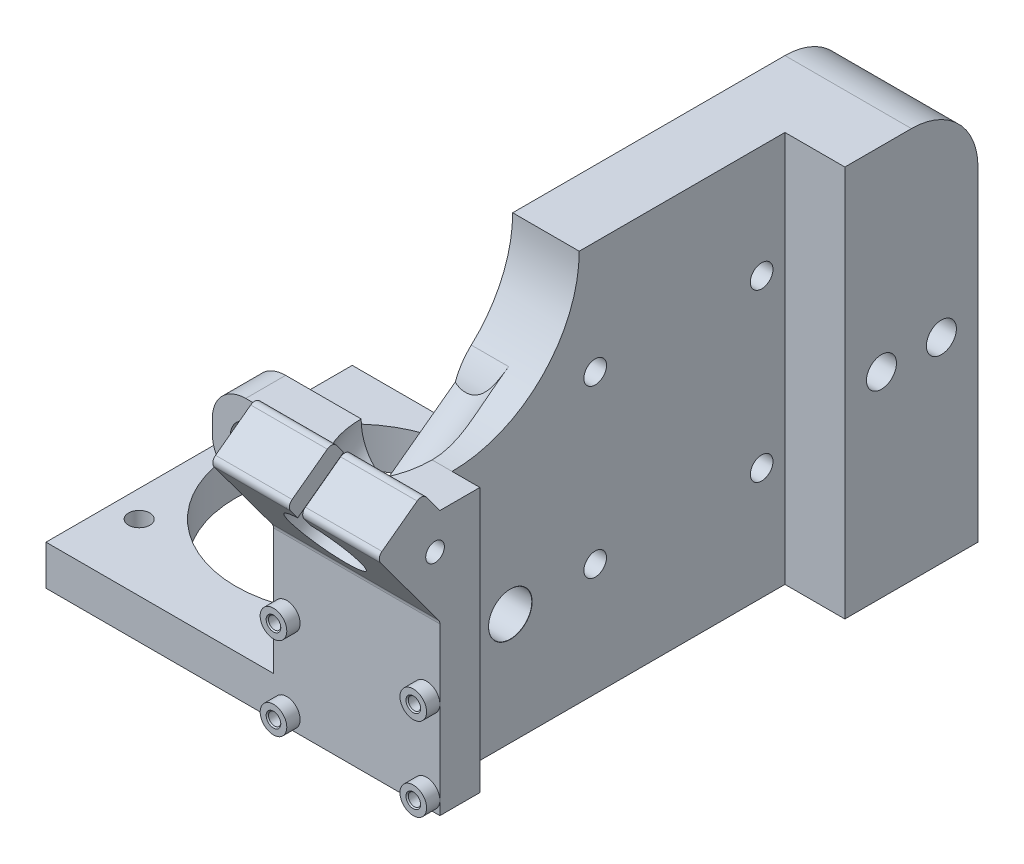
SolidWorks part; units mm, degrees
ref_plane "Front Plane" through (0, 0, 0) normal (0, 0, 1) x (1, 0, 0)
ref_plane "Top Plane" through (0, 0, 0) normal (0, 1, 0) x (1, 0, 0)
ref_plane "Right Plane" through (0, 0, 0) normal (1, 0, 0) x (0, 0, -1)
sketch "Sketch2" plane through (0, 0, 0) normal (0, 0, 1) x (1, 0, 0)
  line L0 (-18.5, 0) -> (18.5, 0) construction
  line L1 (-18.5, 6.1) -> (18.5, 6.1)
  line L2 (-18.5, 6.1) -> (-18.5, -6.1)
  line L3 (-18.5, -6.1) -> (18.5, -6.1)
  line L4 (18.5, 6.1) -> (18.5, -6.1)
  line L5 (-18.5, 6.1) -> (18.5, -6.1) construction
  line L6 (-18.5, -6.1) -> (18.5, 6.1) construction
  circle A0 centre (-5.08, 0) radius 1.5 construction
  circle A1 centre (12.42, 0) radius 1.5
  point P0 (0, 0)
  dimension "D5" = 3
  dimension "D1" = 12.2
  dimension "D2" = 37
  dimension "D3" = 13.42
  dimension "D4" = 17.5
extrude "Boss-Extrude2" add sketch "Sketch2" along normal blind 6
hole_wizard "CBORE for M3 SHCS1" positions "Sketch6" profile "Sketch7" counterbore size "M3" standard "ANSI Metric" end condition through all
sketch "Sketch6" plane through (0, 0, 6) normal (0, 0, 1) x (1, 0, 0)
  point P3 (12.42, 0)
sketch "Sketch7" plane through (12.42, 0, 6) normal (1, 0, 0) x (0, -1, 0)
  line L0 (0, 0) -> (0, 6)
  line L1 (0, 6) -> (1.7, 6)
  line L3 (1.7, 6) -> (1.7, 3)
  line L4 (1.7, 3) -> (3.25, 3)
  line L5 (3.25, 3) -> (3.25, 0)
  line L7 (3.25, 0) -> (0, 0)
  line L11 (0, -6.35) -> (0, 107.95) construction
  dimension "Thru Hole Dia." = 3.4
  dimension "Thru Hole Depth" = 6
  dimension "C'Bore Dia." = 6.5
  dimension "C'Bore Depth" = 3
sketch "Sketch21" plane through (0, 0, 6) normal (0, 0, 1) x (1, 0, 0)
  line L0 (-18.5, -6.1) -> (18.5, -6.1) construction
  line L1 (-12.5, -6.1) -> (-18.5, -6.1)
  line L2 (-12.5, -6.1) -> (-12.5, -27.6)
  line L3 (-12.5, -27.6) -> (-18.5, -27.6)
  line L4 (-18.5, -6.1) -> (-18.5, -27.6)
  point P4 (-18.5, -6.1)
  dimension "D1" = 21.5
  dimension "D2" = 6
extrude "Boss-Extrude6" add sketch "Sketch21" against normal blind 6
sketch "Sketch22" plane through (0, 0, 6) normal (0, 0, 1) x (1, 0, 0)
  line L1 (-18.5, -27.6) -> (21.5, -27.6)
  line L2 (-18.5, -27.6) -> (-18.5, -33.6)
  line L3 (-18.5, -33.6) -> (21.5, -33.6)
  line L4 (21.5, -27.6) -> (21.5, -33.6)
  line L5 (18.5, -6.1) -> (18.5, 6.1) construction
  dimension "D1" = 6
  dimension "D2" = 3
extrude "Boss-Extrude7" add sketch "Sketch22" against normal blind 6
sketch "Sketch23" plane through (0, 0, 6) normal (0, 0, 1) x (1, 0, 0)
  line L0 (-18.5, -33.6) -> (21.5, -33.6) construction
  line L1 (15.67, 6.1) -> (40.67, 6.1)
  line L2 (15.67, 6.1) -> (15.67, -33.6)
  line L3 (15.67, -33.6) -> (40.67, -33.6)
  line L4 (40.67, 6.1) -> (40.67, -33.6)
  line L6 (-18.5, 6.1) -> (-18.5, -33.6) construction
  circle A0 centre (12.42, 0) radius 3.25 construction
  dimension "D1" = 25
extrude "Boss-Extrude8" add sketch "Sketch23" against normal blind 6
sketch "Sketch24" plane through (0, -27.6, 0) normal (0, -1, 0) x (1, 0, 0)
  line L1 (-18.5, 0) -> (21.5, 0)
  line L2 (-18.5, 0) -> (-18.5, -40)
  line L3 (-18.5, -40) -> (21.5, -40)
  line L4 (21.5, 0) -> (21.5, -40)
  line L5 (-18.5, -31.0949) -> (-18.5, -3) construction
  line L6 (21.5, -3) -> (21.5, -19.75) construction
  line L9 (-18.5, 0) -> (40.67, 0) construction
  line L12 (20.3129, -40) -> (-17.3129, -40) construction
  circle A0 centre (17.5, -4) radius 1.25 construction
  circle A1 centre (-14.5, -4) radius 1.55 construction
  circle A2 centre (17.5, -4) radius 1.25 construction
  circle A3 centre (-14.5, -4) radius 1.55 construction
  circle A4 centre (17.5, -36) radius 1.25 construction
  circle A5 centre (17.5, -36) radius 1.25 construction
  circle A6 centre (17.5, -4) radius 1.6
  circle A7 centre (-14.5, -4) radius 1.6
  circle A8 centre (17.5, -36) radius 1.6
  dimension "D1" = 3.2
extrude "Boss-Extrude9" add sketch "Sketch24" along normal up to surface (6 mm away) up to face at (11.085, -33.6, 3)
sketch "Sketch25" plane through (0, -33.6, 0) normal (0, -1, 0) x (1, 0, 0)
  line L0 (21.5, -20) -> (-18.5, -20) construction
  line L1 (21.5, -40) -> (21.5, 0) construction
  line L2 (-18.5, -40) -> (-18.5, 6) construction
  circle A0 centre (1.5, -20) radius 17.5
  dimension "D1" = 35
extrude "Cut-Extrude9" cut sketch "Sketch25" against normal up to next
sketch "Sketch26" plane through (0, 0, 6) normal (0, 0, 1) x (1, 0, 0)
  line L1 (40.67, -33.6) -> (15.67, -33.6) construction
  line L2 (40.67, -33.6) -> (40.67, -9.6) construction
  line L3 (40.67, -9.6) -> (15.67, -9.6) construction
  line L4 (15.67, -33.6) -> (15.67, -9.6) construction
  line L5 (17.67, -31.6) -> (38.67, -31.6) construction
  line L6 (17.67, -31.6) -> (17.67, -19.1) construction
  line L7 (17.67, -19.1) -> (38.67, -19.1) construction
  line L8 (38.67, -31.6) -> (38.67, -19.1) construction
  circle A0 centre (38.67, -31.6) radius 2
  circle A1 centre (17.67, -31.6) radius 2
  circle A2 centre (17.67, -19.1) radius 2
  circle A3 centre (38.67, -19.1) radius 2
  dimension "D1" = 25
  dimension "D2" = 24
  dimension "D3" = 2
  dimension "D4" = 21
  dimension "D5" = 12.5
  dimension "D6" = 2
extrude "Boss-Extrude10" add sketch "Sketch26" along normal blind 2
hole_wizard "M2x0.4 Tapped Hole1" positions "Sketch27" profile "Sketch29" tap size "M2x0.4" standard "ANSI Metric"
sketch "Sketch27" plane through (0, 0, 8) normal (0, 0, 1) x (1, 0, 0)
  circle A0 centre (38.67, -31.6) radius 2 construction
  circle A1 centre (38.67, -19.1) radius 2 construction
  circle A2 centre (17.67, -19.1) radius 2 construction
  circle A3 centre (17.67, -31.6) radius 2 construction
  point P0 (17.67, -31.6)
  point P2 (17.67, -19.1)
  point P4 (38.67, -19.1)
  point P6 (38.67, -31.6)
sketch "Sketch29" plane through (17.67, -31.6, 8) normal (1, 0, 0) x (0, -1, 0)
  line L0 (0, 0) -> (0, 8.5558)
  line L1 (0, 8.5558) -> (0.925, 8)
  line L2 (0.925, 8) -> (0.925, 0.175)
  line L3 (0.925, 0.175) -> (1.1, 0)
  line L5 (1.1, 0) -> (0, 0)
  line L6 (-0.925, 0.175) -> (-1.1, 0) construction
  line L10 (0, 8.5558) -> (-0.925, 8) construction
  line L11 (0, -6.35) -> (0, 107.95) construction
  dimension "Tap Drill Dia." = 1.85
  dimension "Tap Drill Depth" = 8
  dimension "Near C'Sink Dia." = 2.2
  dimension "Near C'Sink Angle" = 90
  dimension "Drill Angle" = 118
cosmetic thread "Hole Thread9" parameters "D1"=4, "D2"=2
cosmetic thread "Hole Thread10" parameters "D1"=4, "D2"=2
cosmetic thread "Hole Thread11" parameters "D1"=4, "D2"=2
cosmetic thread "Hole Thread12" parameters "D1"=4, "D2"=2
sketch "Sketch35" plane through (40.67, 0, 0) normal (1, 0, 0) x (0, 0, -1)
  line L0 (-6, -8.3312) -> (-15.5053, 4.5393)
  line L1 (-6, -19.1) -> (-6, 6.1) construction
  line L2 (-15.5053, 4.5393) -> (-8.6089, 9.6325)
  line L3 (-8.6089, 9.6325) -> (-6, 6.1)
  line L4 (-6, 6.1) -> (-6, -8.3312)
  line L5 (-6, -31.6) -> (-50.9729, -31.6) construction
  line L6 (-50.9729, -31.6) -> (-10.7526, -1.896) construction
  line L7 (-6, -8.3312) -> (0, -3.9) construction
  line L8 (0, -33.6) -> (0, 6.1) construction
  point P7 (-8.7475, 9.5301)
  dimension "D1" = 16
  dimension "D2" = 50
  dimension "D3" = 7.4589
  dimension "D4" = 10
extrude "Boss-Extrude12" add sketch "Sketch35" against normal blind 25
fillet "Fillet1" radius 1 3 edges at (28.17, 4.5393, 15.5053) (28.17, -8.3312, 6) (28.17, 9.6325, 8.6089)
sketch "Sketch45" plane through (0, 0, -40) normal (0, 0, -1) x (-1, 0, 0)
  line L0 (-21.5, -33.6) -> (-21.5, -27.6) construction
  line L1 (-21.5, -33.6) -> (-26.5, -33.6)
  line L2 (-21.5, -33.6) -> (-21.5, -27.6)
  line L3 (-21.5, -27.6) -> (-26.5, -27.6)
  line L4 (-26.5, -33.6) -> (-26.5, -27.6)
  line L5 (18.5, -27.6) -> (-21.5, -27.6) construction
  dimension "D1" = 5
extrude "Boss-Extrude16" add sketch "Sketch45" against normal up to next
sketch "Sketch46" plane through (0, 0, 0) normal (0, 0, -1) x (-1, 0, 0)
  line L1 (-26.5, -33.6) -> (-36.5, -33.6)
  line L2 (-26.5, -33.6) -> (-26.5, -0.9)
  line L3 (-26.5, -0.9) -> (-36.5, -0.9)
  line L4 (-36.5, -33.6) -> (-36.5, -0.9)
  line L5 (-40.67, 6.1) -> (18.5, 6.1) construction
  dimension "D1" = 10
  dimension "D2" = 7
extrude "Boss-Extrude20" add sketch "Sketch46" along normal offset from surface (50 mm away) 10 up to face at (4, -30.6, -40) offset beyond the face yes
sketch "Sketch48" plane through (36.5, 0, 0) normal (1, 0, 0) x (0, 0, -1)
  line L0 (0, 6.1) -> (-6, 6.1) construction
  line L1 (50, -0.9) -> (0, -0.9)
  line L2 (50, -0.9) -> (50, 25.2)
  line L3 (50, 25.2) -> (19.1, 25.2)
  line L6 (50, -33.6) -> (40, -33.6) construction
  line L8 (0, -0.9) -> (0, -33.6) construction
  line L9 (50, -0.9) -> (0, -0.9) construction
  line L10 (0, -33.6) -> (0, 6.1) construction
  line L11 (0, -0.9) -> (0, 6.1)
  line L12 (19.1, 25.2) -> (0, 6.1) construction
  arc A0 (0, 6.1) -> (19.1, 25.2) centre (0, 25.2) ccw
  dimension "D1" = 58.8
  dimension "D2" = 30.9
extrude "Boss-Extrude22" add sketch "Sketch48" against normal blind 10
sketch "Sketch53" plane through (26.5, 0, 0) normal (-1, 0, 0) x (0, 0, 1)
  line L1 (-50, -33.6) -> (-70, -33.6)
  line L2 (-50, -33.6) -> (-50, 25.2)
  line L3 (-50, 25.2) -> (-70, 25.2)
  line L4 (-70, -33.6) -> (-70, 25.2)
  dimension "D1" = 20
extrude "Boss-Extrude23" add sketch "Sketch53" against normal blind 19
sketch "Sketch54" plane through (45.5, 0, 0) normal (1, 0, 0) x (0, 0, -1)
  line L0 (50, -4.2) -> (70, -4.2) construction
  line L1 (50, -33.6) -> (50, 25.2) construction
  line L2 (70, 25.2) -> (70, -33.6) construction
  circle A0 centre (64.5, -4.2) radius 2.25
  circle A1 centre (55.5, -4.2) radius 2.25
  dimension "D1" = 4.5
  dimension "D2" = 5.5
  dimension "D3" = 5.5
extrude "Cut-Extrude14" cut sketch "Sketch54" against normal blind 20
sketch "Sketch56" plane through (26.5, 0, 0) normal (-1, 0, 0) x (0, 0, 1)
  line L1 (-66.5207, -0.7) -> (-68.5415, -4.2)
  line L2 (-68.5415, -4.2) -> (-66.5207, -7.7)
  line L3 (-66.5207, -7.7) -> (-62.4793, -7.7)
  line L4 (-62.4793, -7.7) -> (-60.4585, -4.2)
  line L5 (-60.4585, -4.2) -> (-62.4793, -0.7)
  line L6 (-62.4793, -0.7) -> (-66.5207, -0.7)
  line L7 (-57.5207, -0.7) -> (-59.5415, -4.2)
  line L8 (-59.5415, -4.2) -> (-57.5207, -7.7)
  line L9 (-57.5207, -7.7) -> (-53.4793, -7.7)
  line L10 (-53.4793, -7.7) -> (-51.4585, -4.2)
  line L11 (-51.4585, -4.2) -> (-53.4793, -0.7)
  line L12 (-53.4793, -0.7) -> (-57.5207, -0.7)
  circle A0 centre (-64.5, -4.2) radius 3.5 construction
  circle A1 centre (-55.5, -4.2) radius 3.5 construction
  dimension "D1" = 7
  dimension "D2" = 7
extrude "Cut-Extrude16" cut sketch "Sketch56" against normal blind 11
sketch "Sketch36" plane through (0, -5.8076, 7.8637) normal (0, -0.5941, 0.8044) x (1, 0, 0)
  line L0 (28.17, -3.1372) -> (28.17, 12.8628) construction
  line L1 (15.67, -3.1372) -> (40.67, -3.1372) construction
  line L2 (15.67, 12.8628) -> (40.67, 12.8628) construction
  circle A0 centre (28.17, 4.8628) radius 5.334
  dimension "D1" = 10.668
extrude "Cut-Extrude10" cut sketch "Sketch36" against normal blind 18.668
sketch "Sketch37" plane through (0, 5.2827, -7.1529) normal (0, -0.5941, 0.8044) x (1, 0, 0)
  line L4 (32.7709, 2.1641) -> (26.5, 2.1641)
  line L7 (26.5, 2.1641) -> (26.5, -0.203)
  line L9 (26.5, 2.1641) -> (26.5, -0.203)
  line L10 (32.7709, 2.1641) -> (26.5, 2.1641)
  arc A1 (26.5, -0.203) -> (32.7709, 2.1641) centre (28.17, 4.8628) ccw
  arc A2 (26.5, -0.203) -> (32.7709, 2.1641) centre (28.17, 4.8628) ccw
  dimension "D1" = 0
sketch "Sketch38" plane through (40.67, 0, 0) normal (1, 0, 0) x (0, 0, -1)
  line L0 (-13.9215, 2.3947) -> (-7.5838, -6.1867) construction
  line L1 (-13.9215, 2.3947) -> (-7.5838, -6.1867) construction
  line L2 (-10.7526, -1.896) -> (0.0742, 6.1) construction
  line L3 (0, 6.1) -> (-6, 6.1) construction
  circle A0 centre (-6.7306, 1.0744) radius 1.4
  dimension "D1" = 2.8
  dimension "D2" = 5
extrude "Cut-Extrude12" cut sketch "Sketch38" against normal up to next
sketch "Sketch69" plane through (0, -33.6, 0) normal (0, -1, 0) x (1, 0, 0)
  line L0 (45.5, -70) -> (26.5, -70) construction
  line L1 (26.5, -40) -> (14.5, -40)
  line L2 (26.5, -40) -> (26.5, -70)
  line L3 (26.5, -70) -> (14.5, -70)
  line L4 (14.5, -40) -> (14.5, -70)
  line L6 (36.5, -50) -> (36.5, 0) construction
  dimension "D1" = 22
extrude "Boss-Extrude24" add sketch "Sketch69" against normal up to surface (6 mm away) up to face at (-16, -27.6, -20)
sketch "Sketch57" plane through (60.1, -33.6, 0) normal (0, 1, 0) x (0, 0, 1)
  line L1 (-68, -42.68) -> (-55.3, -42.68)
  line L2 (-68, -42.68) -> (-68, -21.18)
  line L3 (-68, -21.18) -> (-55.3, -21.18)
  line L4 (-55.3, -42.68) -> (-55.3, -21.18)
  line L6 (6, -31.93) -> (-55.3, -31.93) construction
  line L7 (6, -42.43) -> (6, -21.43) construction
  line L8 (-70, -14.6) -> (-70, -45.6) construction
  dimension "D1" = 21.5
  dimension "D2" = 12.7
  dimension "D3" = 2
hole_wizard "CBORE for M3 SHCS3" positions "Sketch58" profile "Sketch59" counterbore size "M3" standard "ANSI Metric"
sketch "Sketch58" plane through (26.5, 0, 0) normal (-1, 0, 0) x (0, 0, 1)
  line L1 (-46.5, -16.7) -> (-21.5, -16.7)
  line L2 (-46.5, -16.7) -> (-46.5, 8.3)
  line L3 (-46.5, 8.3) -> (-21.5, 8.3)
  line L4 (-21.5, -16.7) -> (-21.5, 8.3)
  line L5 (0, -27.6) -> (0, -0.2524) construction
  line L6 (-70, 25.2) -> (-19.1, 25.2) construction
  point P0 (-46.5, -16.7)
  point P2 (-46.5, 8.3)
  point P4 (-21.5, 8.3)
  point P6 (-21.5, -16.7)
  point P97 (-46.5, 8.3)
  point P100 (-21.5, -16.7)
  dimension "D1" = 21.5
  dimension "D2" = 25
  dimension "D3" = 16.9
sketch "Sketch59" plane through (26.5, -16.7, -46.5) normal (0, 1, 0) x (0, 0, 1)
  line L0 (0, 0) -> (0, 13.0215)
  line L1 (0, 13.0215) -> (1.7, 12)
  line L2 (1.7, 12) -> (1.7, 3)
  line L3 (1.7, 3) -> (3.25, 3)
  line L4 (3.25, 3) -> (3.25, 0)
  line L5 (3.25, 0) -> (0, 0)
  line L10 (0, 13.0215) -> (-1.7, 12) construction
  line L11 (0, -6.35) -> (0, 107.95) construction
  dimension "Hole Dia." = 3.4
  dimension "Hole Depth" = 12
  dimension "C'Bore Dia." = 6.5
  dimension "C'Bore Depth" = 3
  dimension "Drill Angle" = 118
fillet "Fillet7" radius 10 2 edges at (36, 25.2, -70) (14.5, -30.6, -40)
hole_wizard "M2x0.4 Tapped Hole2" positions "Sketch60" profile "Sketch61" tap size "M2x0.4" standard "ANSI Metric"
sketch "Sketch60" plane through (-7.1, -33.6, 0) normal (0, -1, 0) x (0, 0, 1)
  point P0 (-68, -24.52)
  point P3 (-68, -46.02)
  point P6 (-55.3, -46.02)
  point P9 (-55.3, -24.52)
cosmetic thread "Hole Thread13" parameters "D1"=6, "D2"=2
cosmetic thread "Hole Thread14" parameters "D1"=6, "D2"=2
cosmetic thread "Hole Thread15" parameters "D1"=6, "D2"=2
cosmetic thread "Hole Thread16" parameters "D1"=6, "D2"=2
sketch "Sketch61" plane through (17.42, -33.6, -68) normal (1, 0, 0) x (0, 0, -1)
  line L0 (0, 0) -> (0, 7.7558)
  line L1 (0, 7.7558) -> (0.925, 7.2)
  line L2 (0.925, 7.2) -> (0.925, 0.175)
  line L3 (0.925, 0.175) -> (1.1, 0)
  line L5 (1.1, 0) -> (0, 0)
  line L6 (-0.925, 0.175) -> (-1.1, 0) construction
  line L10 (0, 7.7558) -> (-0.925, 7.2) construction
  line L11 (0, -6.35) -> (0, 107.95) construction
  dimension "Tap Drill Dia." = 1.85
  dimension "Tap Drill Depth" = 7.2
  dimension "Near C'Sink Dia." = 2.2
  dimension "Near C'Sink Angle" = 90
  dimension "Drill Angle" = 118
sketch "Sketch62" plane through (36.5, 0, 0) normal (1, 0, 0) x (0, 0, -1)
  circle A0 centre (8.75, -16.85) radius 1.25 construction
  circle A1 centre (8.75, -16.85) radius 1.25
hole_wizard "CBORE for M3 SHCS4" positions "Sketch64" profile "Sketch65" counterbore size "M3" standard "ANSI Metric" end condition through all
sketch "Sketch64" plane through (36.5, 0, 0) normal (1, 0, 0) x (0, 0, -1)
  point P0 (8.75, -16.85)
sketch "Sketch65" plane through (36.5, -16.85, -8.75) normal (0, 1, 0) x (0, 0, -1)
  line L0 (0, 0) -> (0, 55)
  line L1 (0, 55) -> (1.7, 55)
  line L3 (1.7, 55) -> (1.7, 5)
  line L4 (3.25, 5) -> (1.7, 5)
  line L5 (3.25, 5) -> (3.25, 0.025)
  line L6 (3.25, 0.025) -> (3.275, 0)
  line L7 (3.275, 0) -> (0, 0)
  line L8 (-3.25, 0.025) -> (-3.275, 0) construction
  line L11 (0, -6.35) -> (0, 107.95) construction
  dimension "Thru Hole Dia." = 3.4
  dimension "Thru Hole Depth" = 55
  dimension "C'Bore Dia." = 6.5
  dimension "C'Bore Depth" = 5
  dimension "Near C'Sink Dia." = 6.55
  dimension "Near C'Sink Angle" = 90
sketch "Sketch66" plane through (0, -0.7144, 0.9673) normal (0, 0.5941, -0.8044) x (-1, 0, 0)
  line L0 (-28.17, 4.8628) -> (-28.17, 18.8628) construction
  line L1 (-27.17, 4.8628) -> (-27.17, 18.8628)
  line L2 (-29.17, 4.8628) -> (-29.17, 18.8628)
  arc A1 (-24.2419, 8.4714) -> (-32.0981, 8.4714) centre (-28.17, 4.8628) ccw construction
  arc A2 (-27.17, 4.8628) -> (-29.17, 4.8628) centre (-28.17, 4.8628) cw
  arc A3 (-27.17, 18.8628) -> (-29.17, 18.8628) centre (-28.17, 18.8628) ccw
  point P0 (-28.4997, 19.0023)
  dimension "D1" = 14
  dimension "D2" = 1
  dimension "D3" = 1
extrude "Cut-Extrude17" cut sketch "Sketch66" against normal blind 10
fillet "Fillet9" radius 9 1 edges at (29.6355, 7.0235, -5.8672)
sketch "Sketch67" plane through (0, 0, 0) normal (0, 0, -1) x (-1, 0, 0)
  line L0 (-22.8362, 6.1) -> (18.5, 6.1) construction
  line L1 (18.5, -27.6) -> (-6.5, -27.6)
  line L2 (18.5, -27.6) -> (18.5, 6.1)
  line L3 (18.5, 6.1) -> (-6.5, 6.1)
  line L4 (-6.5, -27.6) -> (-6.5, 6.1)
  dimension "D1" = 25
extrude "Cut-Extrude18" cut sketch "Sketch67" against normal blind 10
fillet "Fillet10" radius 5 2 edges at (6.5, -6.1, 3) (6.5, 6.1, 3)
